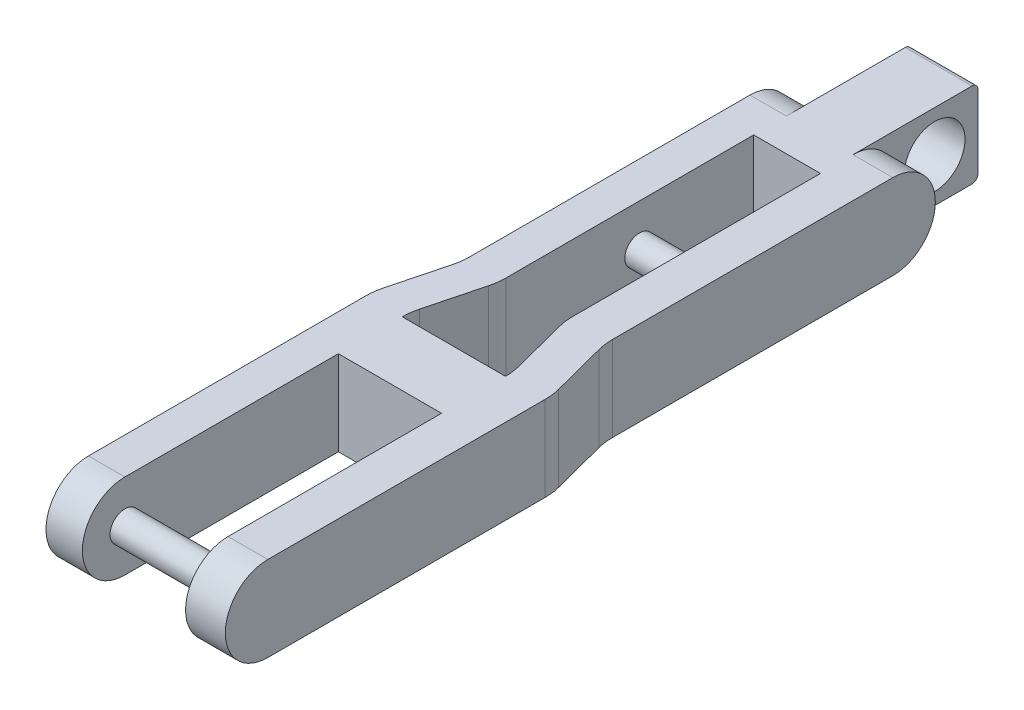
SolidWorks part; units mm, degrees
ref_plane "前视基准面" through (0, 0, 0) normal (0, 0, 1) x (1, 0, 0)
ref_plane "上视基准面" through (0, 0, 0) normal (0, 1, 0) x (1, 0, 0)
ref_plane "右视基准面" through (0, 0, 0) normal (1, 0, 0) x (0, 0, -1)
sketch "草图1" plane through (0, 0, 0) normal (0, 1, 0) x (1, 0, 0)
  line L0 (-5, 0) -> (5, 0) construction
  line L1 (5, 0) -> (5, 52.718)
  line L2 (4.6766, 55.2405) -> (2.3234, 64.2681)
  line L3 (2, 66.7906) -> (2, 120)
  line L4 (5, 0) -> (-1.5534, 0)
  line L5 (-1.5534, 0) -> (-1.5534, 52.718)
  line L6 (-1.8768, 55.2405) -> (-4.2301, 64.2681)
  line L7 (-4.5534, 66.7906) -> (-4.5534, 120)
  line L8 (-4.5534, 120) -> (2, 120)
  arc A0 (-4.2301, 64.2681) -> (-4.5534, 66.7906) centre (5.4466, 66.7906) cw
  arc A1 (2.3234, 64.2681) -> (2, 66.7906) centre (12, 66.7906) cw
  arc A2 (5, 52.718) -> (4.6766, 55.2405) centre (-5, 52.718) ccw
  arc A3 (-1.5534, 52.718) -> (-1.8768, 55.2405) centre (-11.5534, 52.718) ccw
  point P4 (0, 0)
  point P14 (-4.5534, 65.5086)
  point P17 (2, 65.5086)
  point P20 (5, 54)
  point P23 (-1.5534, 54)
  dimension "D8" = 10
  dimension "D9" = 10
  dimension "D10" = 10
  dimension "D11" = 10
  dimension "D1" = 10
  dimension "D2" = 54
  dimension "D3" = 120
  dimension "D4" = 3
  dimension "D5" = 6.5534
  dimension "D6" = 54
  dimension "D7" = 3
extrude "凸台-拉伸2" add sketch "草图1" along normal blind 14
fillet "圆角1" 2 edges at (1.7233, 14, 0) (1.7233, 0, 0) type full round first side face at (0.2233, 14, -59.8362) second side face at (0.2233, 0, -59.8362) middle face at (1.7233, 7, 0)
fillet "圆角2" 2 edges at (-1.2767, 14, -120) (-1.2767, 0, -120) type full round first side face at (0.2233, 14, -61.0029) second side face at (0.2233, 0, -61.0029) middle face at (-1.2767, 7, -120)
sketch "草图4" plane through (0, 0, 0) normal (0, 1, 0) x (1, 0, 0)
  line L0 (0, 0) -> (-67.1091, 0) construction
  line L1 (-18.5534, 0) -> (-24.5534, 0)
  line L2 (-24.5534, 0) -> (-24.5534, 52.718)
  line L3 (-24.2301, 55.2405) -> (-21.8768, 64.2681)
  line L4 (-21.5534, 66.7906) -> (-21.5534, 120)
  line L5 (-21.5534, 120) -> (-15.5534, 120)
  line L6 (-15.5534, 120) -> (-15.5534, 66.7906)
  line L7 (-15.8768, 64.2681) -> (-18.2301, 55.2405)
  line L8 (-18.5534, 52.718) -> (-18.5534, 0)
  line L9 (2, 66.7906) -> (-28.166, 66.7906) construction
  line L10 (-4.5534, 113) -> (-4.5534, 66.7906) construction
  arc A0 (2, 66.7906) -> (2.3234, 64.2681) centre (12, 66.7906) ccw construction
  arc A1 (-18.2301, 55.2405) -> (-18.5534, 52.718) centre (-8.5534, 52.718) ccw
  arc A2 (-24.5534, 52.718) -> (-24.2301, 55.2405) centre (-14.5534, 52.718) cw
  arc A3 (-15.5534, 66.7906) -> (-15.8768, 64.2681) centre (-25.5534, 66.7906) cw
  arc A4 (-21.8768, 64.2681) -> (-21.5534, 66.7906) centre (-31.5534, 66.7906) ccw
  point P16 (-18.5534, 54)
  point P19 (-24.5534, 54)
  point P22 (-15.5534, 65.5086)
  dimension "D8" = 10
  dimension "D1" = 6
  dimension "D2" = 54
  dimension "D3" = 54
  dimension "D4" = 120
  dimension "D5" = 6
  dimension "D6" = 3
  dimension "D7" = 11
extrude "凸台-拉伸3" add sketch "草图4" along normal blind 14 separate body
fillet "圆角3" 2 edges at (-18.5534, 14, -120) (-18.5534, 0, -120) type full round first side face at (-20.0534, 14, -59.8362) second side face at (-20.0534, 0, -59.8362) middle face at (-18.5534, 7, -120)
fillet "圆角4" 2 edges at (-21.5534, 0, 0) (-21.5534, 14, 0) type full round first side face at (-20.0534, 0, -58.6695) second side face at (-20.0534, 14, -58.6695) middle face at (-21.5534, 7, 0)
sketch "草图8" plane through (-18.5534, 0, 0) normal (1, 0, 0) x (0, 0, -1)
  line L1 (52.718, 14) -> (42.1796, 14)
  line L2 (52.718, 14) -> (52.718, 0)
  line L3 (52.718, 0) -> (42.1796, 0)
  line L6 (42.1796, 14) -> (42.1796, 0)
  circle A0 centre (7, 7) radius 2.45
  dimension "D1" = 4.9
extrude "凸台-拉伸5" add sketch "草图8" along normal up to next
sketch "草图11" plane through (-15.5534, 0, 0) normal (1, 0, 0) x (0, 0, -1)
  line L0 (120, 7) -> (67.3321, 7) construction
  circle A0 centre (88.8037, 7) radius 2.425
  arc A1 (113, 0) -> (113, 14) centre (113, 7) ccw construction
  dimension "D2" = 4.85
extrude "凸台-拉伸6" add sketch "草图11" along normal up to next
sketch "草图13" plane through (-15.5534, 0, 0) normal (1, 0, 0) x (0, 0, -1)
  line L0 (66.7906, 14) -> (113, 14) construction
  line L1 (107.6256, 14) -> (133.5865, 14)
  line L2 (107.6256, 14) -> (107.6256, 0)
  line L3 (107.6256, 0) -> (133.5865, 0)
  line L4 (133.5865, 14) -> (133.5865, 0)
extrude "凸台-拉伸7" add sketch "草图13" along normal blind 11
sketch "草图14" plane through (-15.5534, 0, 0) normal (-1, 0, 0) x (0, 0, 1)
  line L0 (-133.5865, 7) -> (-106.2768, 7) construction
  line L1 (-133.5865, 0) -> (-133.5865, 14) construction
  circle A0 centre (-126.4428, 7) radius 5
  dimension "D1" = 10
extrude "切除-拉伸2" cut sketch "草图14" against normal up to next
fillet "圆角5" radius 1 2 edges at (-10.0534, 14, -133.5865) (-10.0534, 0, -133.5865)
